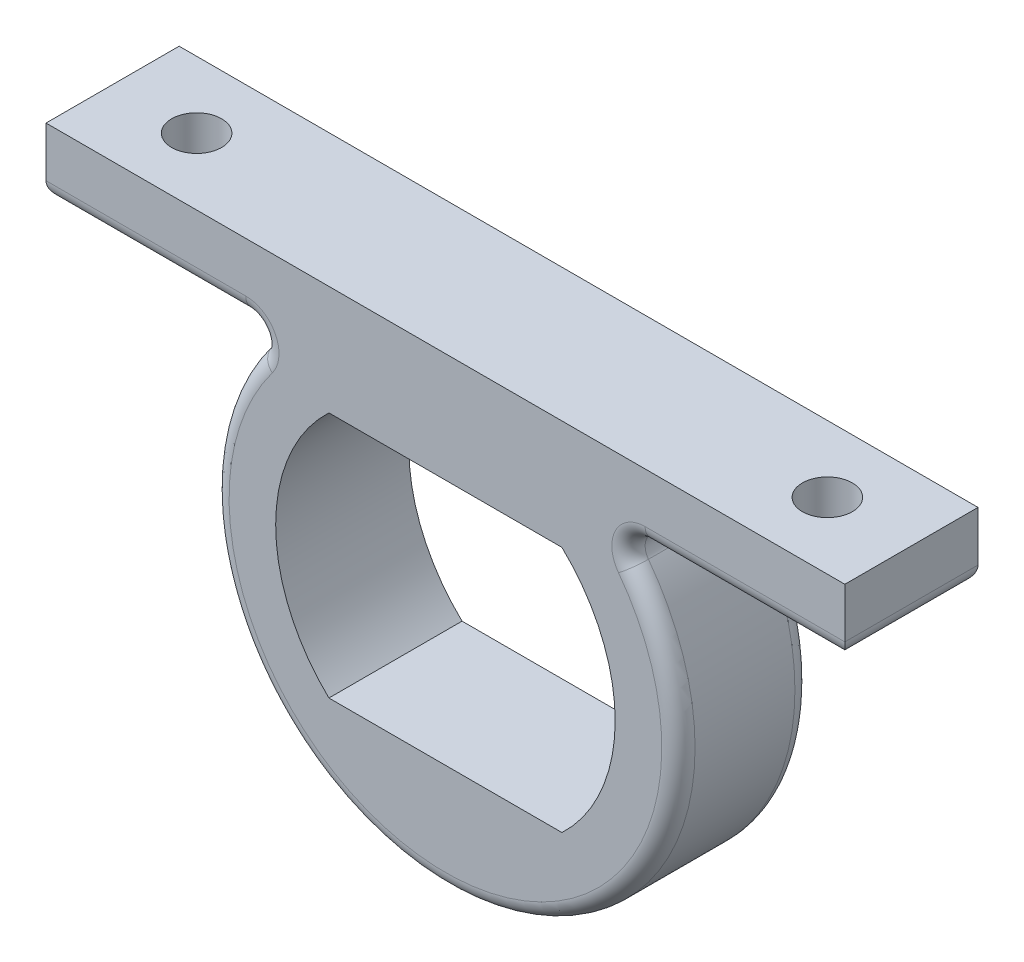
SolidWorks part; units mm, degrees
ref_plane "Alzado" through (0, 0, 0) normal (0, 0, 1) x (1, 0, 0)
ref_plane "Planta" through (0, 0, 0) normal (0, 1, 0) x (1, 0, 0)
ref_plane "Vista lateral" through (0, 0, 0) normal (1, 0, 0) x (0, 0, -1)
sketch "Croquis1" plane through (0, 0, 0) normal (0, 0, 1) x (1, 0, 0)
  line L0 (0, 14) -> (-24, 14)
  line L1 (-24, 14) -> (-24, 10)
  line L2 (-24, 10) -> (-9.798, 10)
  line L3 (0, 14) -> (24, 14)
  line L4 (24, 14) -> (24, 10)
  line L5 (0, -10) -> (0, 10) construction
  line L6 (24, 10) -> (9.798, 10)
  circle A0 centre (0, 0) radius 10
  arc A1 (-9.798, 10) -> (9.798, 10) centre (0, 0) ccw
  dimension "D1" = 20
  dimension "D2" = 48
  dimension "D5" = 24
  dimension "D4" = 4
  dimension "D3" = 14
extrude "Saliente-Extruir1" add sketch "Croquis1" along normal blind 8 contours L4 L6 A1 L2 L1 L0 L3
sketch "Croquis2" plane through (0, 0, 8) normal (0, 0, 1) x (1, 0, 0)
  line L0 (-7, 7.4189) -> (7, 7.4189)
  line L1 (-7, -7.4189) -> (7, -7.4189)
  arc A0 (-7, 7.4189) -> (-7, -7.4189) centre (0, 0) ccw
  arc A1 (7, 7.4189) -> (7, -7.4189) centre (0, 0) cw
  dimension "D1" = 10.2
  dimension "D2" = 14
  dimension "D4" = 10.2
  dimension "D3" = 14
extrude "Cortar-Extruir1" cut sketch "Croquis2" against normal through all
fillet "Redondeo1" radius 1 10 edges at (-16.899, 10, 8) (-16.899, 10, 0) (16.899, 10, 8) (16.899, 10, 0) (-9.798, 10, 4) (0, -14, 8) (9.798, 10, 4) (0, -14, 0) (24, 10, 4) (-24, 10, 4)
sketch "Croquis3" plane through (0, 10, 0) normal (0, -1, 0) x (-1, 0, 0)
  line L0 (23, -7) -> (23, -1) construction
  line L2 (12, -7) -> (23, -7) construction
  line L4 (-23, -7) -> (-12, -7) construction
  line L5 (-23, -1) -> (-23, -7) construction
  circle A0 centre (18.9495, -4) radius 1.5
  circle A1 centre (-18.9495, -4) radius 1.5
  dimension "D1" = 3
  dimension "D2" = 3
  dimension "D3" = 4.0505
  dimension "D4" = 3
  dimension "D5" = 3
  dimension "D6" = 4.0505
extrude "Cortar-Extruir2" cut sketch "Croquis3" against normal through all
